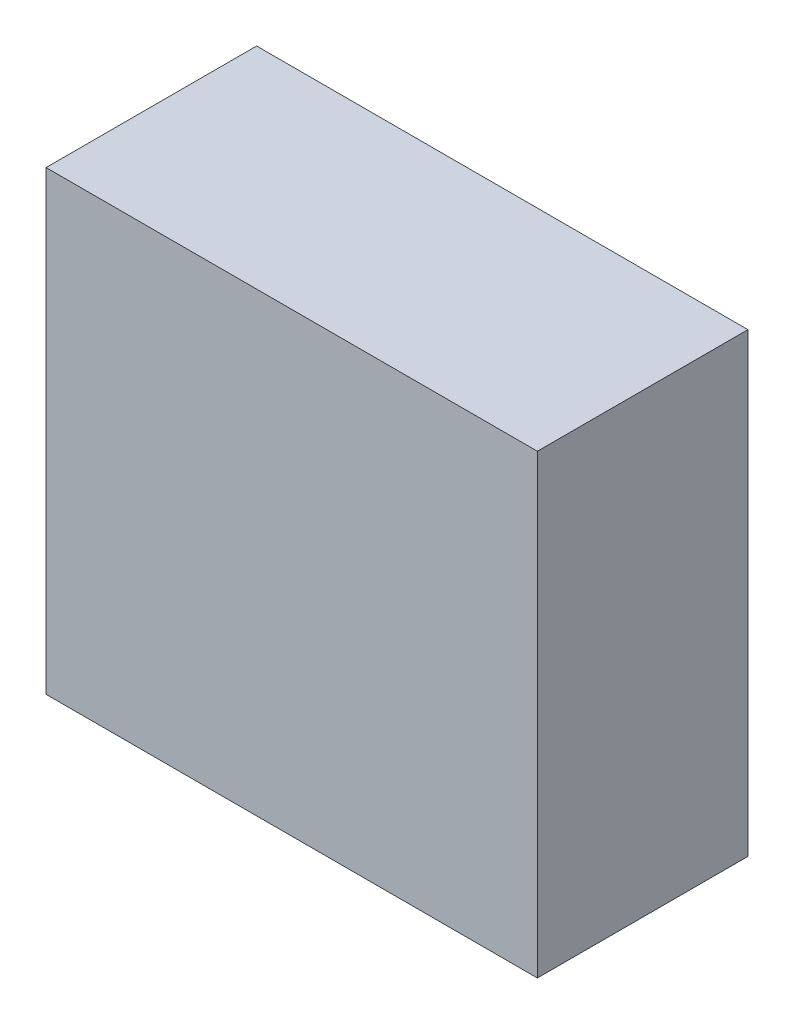
SolidWorks part; units mm, degrees
ref_plane "Front Plane" through (0, 0, 0) normal (0, 0, 1) x (1, 0, 0)
ref_plane "Top Plane" through (0, 0, 0) normal (0, 1, 0) x (1, 0, 0)
ref_plane "Right Plane" through (0, 0, 0) normal (1, 0, 0) x (0, 0, -1)
sketch "Sketch2" plane through (0, 0, 0) normal (0, 0, 1) x (1, 0, 0)
  line L1 (-88.9, 82.55) -> (88.9, 82.55)
  line L2 (-88.9, 82.55) -> (-88.9, -82.55)
  line L3 (-88.9, -82.55) -> (88.9, -82.55)
  line L4 (88.9, 82.55) -> (88.9, -82.55)
  line L5 (-88.9, 82.55) -> (88.9, -82.55) construction
  line L6 (-88.9, -82.55) -> (88.9, 82.55) construction
  point P0 (0, 0)
  dimension "D1" = 165.1
  dimension "D2" = 177.8
extrude "Boss-Extrude1" add sketch "Sketch2" along normal blind 76.2 contours L1 L4 L3 L2
sketch "Sketch3" plane through (0, 82.55, 0) normal (0, 1, 0) x (1, 0, 0)
  text T0 "BATTERY" font "Century Gothic" height 25.4
